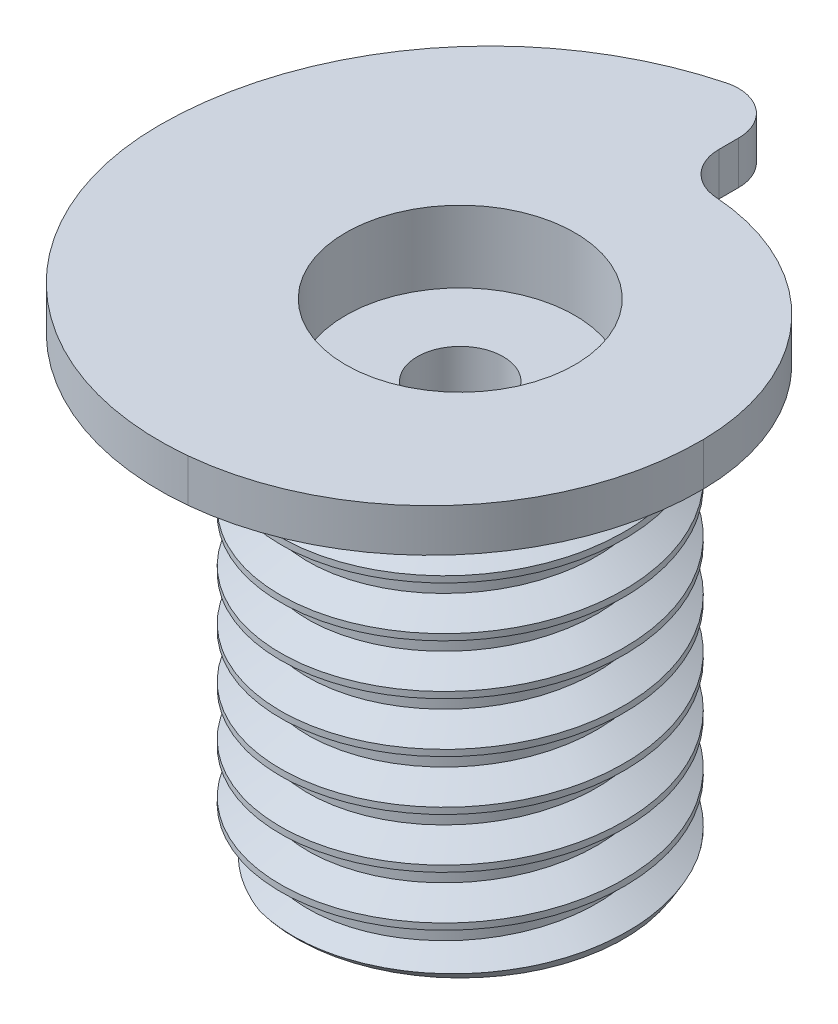
SolidWorks part; units mm, degrees
ref_plane "Front Plane" through (0, 0, 0) normal (0, 0, 1) x (1, 0, 0)
ref_plane "Top Plane" through (0, 0, 0) normal (0, 1, 0) x (1, 0, 0)
ref_plane "Right Plane" through (0, 0, 0) normal (1, 0, 0) x (0, 0, -1)
sketch "Sketch1" plane through (0, 0, 0) normal (1, 0, 0) x (0, 0, -1)
  line L4 (12, 30) -> (12, 0)
  line L6 (0, 0) -> (0, 30) construction
  line L7 (12, 30) -> (3, 30)
  line L10 (3, 30) -> (3, 5)
  line L11 (3, 5) -> (8, 5)
  line L12 (8, 5) -> (8, 0)
  line L13 (8, 0) -> (12, 0)
  point P2 (12, 30)
  point P4 (12, 30)
  point P6 (3, 30)
  point P10 (0, 0)
  point P11 (12.3149, 30)
  dimension "D1" = 8
  dimension "D2" = 6
  dimension "D3" = 5
  dimension "D6" = 30
  dimension "D7" = 12
revolve "Revolve1" add sketch "Sketch1" angle 360 about L6
chamfer "Chamfer1" distance 1 angle 30 1 edges at (0, 0, -12) first distance on face at (0, 30, -12)
thread "Thread1" pitch 3.5 method cut profile "Thread Profile1" start angle 0, offset 0, length 48, pitch 3.5, diameter 24
ref_plane "Plane1" through (-12, 30, 0) normal (0, 0, 1) x (-1, 0, 0)
sketch "Thread Profile1" plane through (-12, 30, 0) normal (0, 0, 1) x (-1, 0, 0)
  line L0 (0, 0) -> (0, 3.5) construction
  line L11 (0, 0) -> (0, 3.0625)
  line L12 (0, 3.0625) -> (-1.8944, 1.9687)
  line L13 (-1.8944, 1.9687) -> (-1.8944, 1.0937)
  line L15 (-1.8944, 1.0937) -> (0, 0)
  line L17 (-1.8944, 1.5312) -> (0, 1.5312) construction
  point P2 (0, 0)
  dimension "Pitch" = 3.5
  dimension "Profile_Angle" = 60
  dimension "Profile_Land" = 0.875
  dimension "Profile_Height" = 1.8944
sketch "Sketch2" plane through (0, 30, 0) normal (0, 1, 0) x (1, 0, 0)
  line L1 (0, 11.547) -> (-10, -5.7735) construction
  line L2 (-10, -5.7735) -> (10, -5.7735) construction
  line L3 (10, -5.7735) -> (0, 11.547) construction
  circle A0 centre (0, 0) radius 5.7735 construction
  circle A1 centre (0, 11.547) radius 1.5
  circle A2 centre (10, -5.7735) radius 1.5
  circle A3 centre (-10, -5.7735) radius 1.5
  dimension "D2" = 3
  dimension "D1" = 20
extrude "Cut-Extrude1" [suppressed] cut sketch "Sketch2" against normal blind 4
sketch "Sketch3" plane through (0, 30, 0) normal (0, 1, 0) x (1, 0, 0)
  line L0 (0, 23) -> (0, -23) construction
  line L1 (-23, 0) -> (23, 0) construction
  line L2 (0, 23) -> (0, 15)
  circle A1 centre (0, 0) radius 15 construction
  circle A2 centre (0, 0) radius 17 construction
  circle A3 centre (0, 0) radius 19 construction
  circle A4 centre (0, 0) radius 21 construction
  circle A5 centre (0, 0) radius 23 construction
  arc A6 (0, 23) -> (-21, 0) centre (2.0952, 0) ccw
  arc A7 (-21, 0) -> (0, -19) centre (-1.9048, 0) ccw
  arc A8 (0, -19) -> (17, 0) centre (-1.8838, -0.2092) ccw
  arc A9 (17, 0) -> (0, 15) centre (1.7331, -0.1692) ccw
  dimension "D1" = 30
  dimension "D2" = 2
  dimension "D3" = 2
  dimension "D4" = 2
  dimension "D5" = 2
extrude "Boss-Extrude1" add sketch "Sketch3" along normal blind 3
sketch "Sketch4" plane through (0, 33, 0) normal (0, 1, 0) x (1, 0, 0)
  circle A2 centre (0, 0) radius 8
  dimension "D1" = 16
extrude "Cut-Extrude2" cut sketch "Sketch4" against normal blind 5
fillet "Fillet1" radius 3 2 edges at (0, 31.5, -15) (0, 31.5, -23)
sketch "Sketch5" plane through (0, 33, 0) normal (0, 1, 0) x (1, 0, 0)
  arc A0 (-6.606, 16.744) -> (-18, 0) centre (0, 0) ccw construction
  arc A1 (-7.5235, 19.0695) -> (-20.5, 0) centre (0, 0) ccw
  arc A2 (-5.6885, 14.4184) -> (-15.5, 0) centre (0, 0) ccw
  arc A3 (-5.6885, 14.4184) -> (-7.5235, 19.0695) centre (-6.606, 16.744) ccw
  arc A4 (-20.5, 0) -> (-15.5, 0) centre (-18, 0) ccw
  arc A5 (-8.6169, -12.278) -> (8.6169, -12.278) centre (0, 0) ccw construction
  arc A6 (-9.7658, -13.9151) -> (9.7658, -13.9151) centre (0, 0) ccw
  arc A7 (-7.4679, -10.6409) -> (7.4679, -10.6409) centre (0, 0) ccw
  arc A8 (-7.4679, -10.6409) -> (-9.7658, -13.9151) centre (-8.6169, -12.278) ccw
  arc A9 (9.7658, -13.9151) -> (7.4679, -10.6409) centre (8.6169, -12.278) ccw
  arc A10 (13.9041, 1.6355) -> (6.0016, 12.6484) centre (0, 0) ccw construction
  arc A11 (15.3939, 1.8107) -> (6.6446, 14.0035) centre (0, 0) ccw
  arc A12 (12.4144, 1.4603) -> (5.3586, 11.2932) centre (0, 0) ccw
  arc A13 (12.4144, 1.4603) -> (15.3939, 1.8107) centre (13.9041, 1.6355) ccw
  arc A14 (6.6446, 14.0035) -> (5.3586, 11.2932) centre (6.0016, 12.6484) ccw
  point P4 (-14.8813, 10.1265)
  point P9 (0, -15)
  point P18 (11.3745, 8.1621)
  point P26 (8.2963, -10.2753)
  point P27 (0, -15)
  point P28 (0, 0)
  point P29 (15.3081, 0)
  point P30 (-12.7716, 12.6841)
  point P31 (-18, 0)
  point P32 (13, 0)
  point P33 (-11.2268, -9.9479)
  point P34 (8.4711, -12.278)
  point P35 (12.911, 1.5187)
  point P36 (5.5729, 11.7449)
  dimension "D1" = 18
  dimension "D2" = 2.5
  dimension "D3" = 15
  dimension "D4" = 2
  dimension "D5" = 14
  dimension "D6" = 1.5
